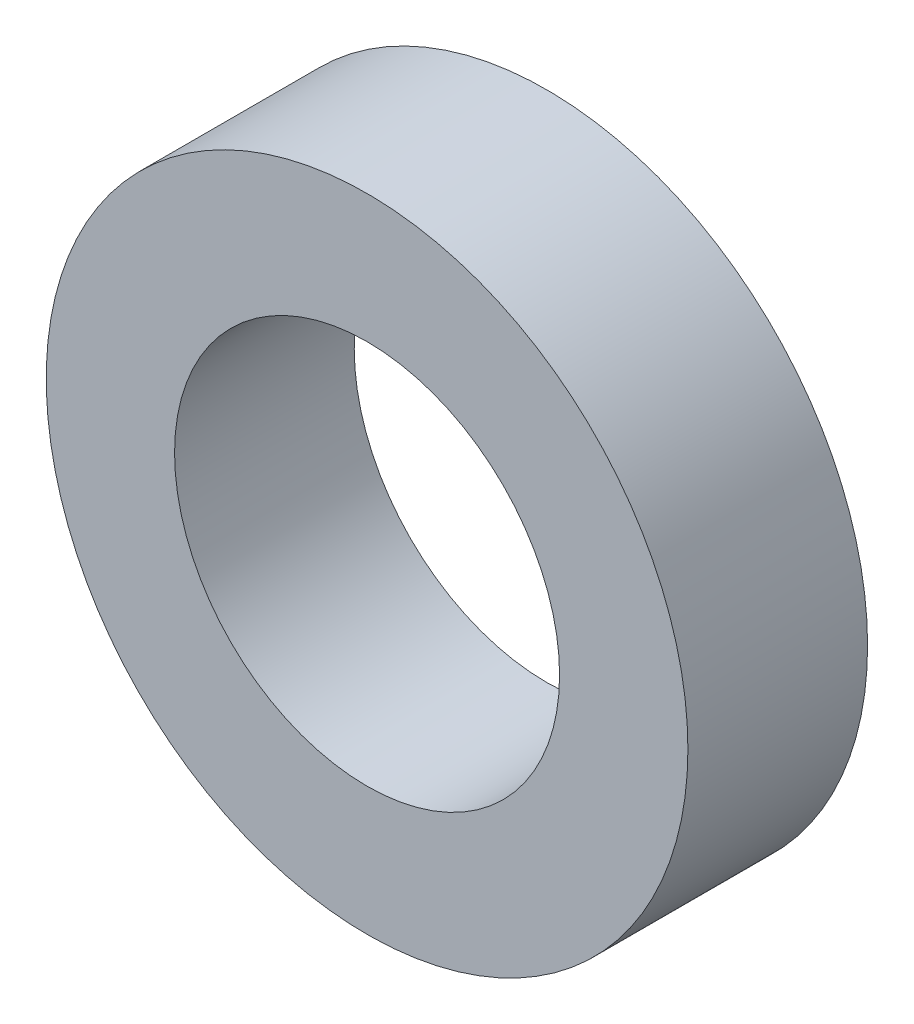
SolidWorks part; units mm, degrees
ref_plane "Front Plane" through (0, 0, 0) normal (0, 0, 1) x (1, 0, 0)
ref_plane "Top Plane" through (0, 0, 0) normal (0, 1, 0) x (1, 0, 0)
ref_plane "Right Plane" through (0, 0, 0) normal (1, 0, 0) x (0, 0, -1)
sketch "Sketch1" plane through (0, 0, 0) normal (0, 0, 1) x (1, 0, 0)
  circle A0 centre (0, 0) radius 15.875
  circle A1 centre (0, 0) radius 9.525
  dimension "D1" = 31.75
  dimension "D2" = 19.05
extrude "Boss-Extrude1" add sketch "Sketch1" along normal blind 8.89
